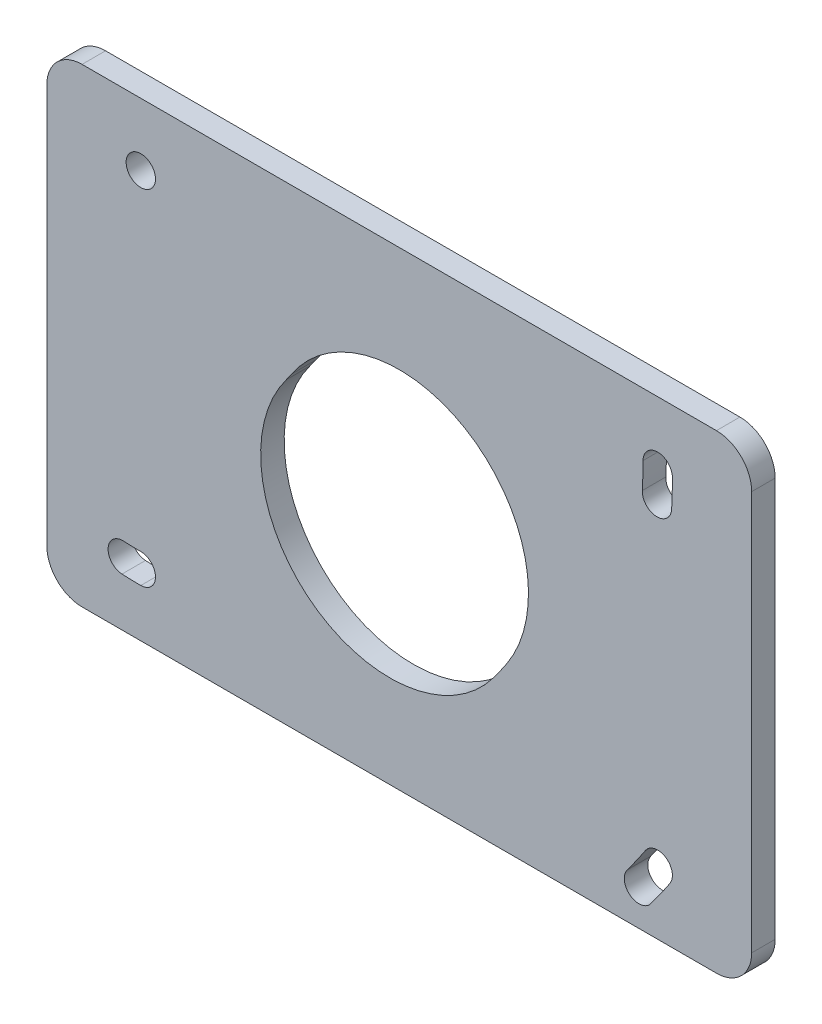
SolidWorks part; units mm, degrees
ref_plane "Płaszczyzna przednia" through (0, 0, 0) normal (0, 0, 1) x (1, 0, 0)
ref_plane "Płaszczyzna górna" through (0, 0, 0) normal (0, 1, 0) x (1, 0, 0)
ref_plane "Płaszczyzna prawa" through (0, 0, 0) normal (1, 0, 0) x (0, 0, -1)
sketch "Szkic1" plane through (0, 0, 0) normal (0, 0, 1) x (1, 0, 0)
  line L0 (-22, 14.6667) -> (-0.7977, -1.1313) construction
  line L1 (-27, -20) -> (27, -20)
  line L2 (-30, -17) -> (-30, 17)
  line L3 (-27, 20) -> (27, 20)
  line L4 (30, -17) -> (30, 17)
  line L5 (-30, -20) -> (30, 20) construction
  line L6 (-30, 20) -> (30, -20) construction
  line L7 (-22, -14.6667) -> (-22, 14.6667) construction
  line L8 (-22, 14.6667) -> (-23.5352, -14.6265) construction
  line L9 (-22, 14.6667) -> (20.4045, -16.9292) construction
  line L10 (22, 14.6667) -> (-22, 14.6667) construction
  line L11 (-22, 14.6667) -> (21.9397, 12.3639) construction
  arc A0 (27, 20) -> (30, 17) centre (27, 17) cw
  arc A1 (27, -20) -> (30, -17) centre (27, -17) ccw
  arc A2 (-27, -20) -> (-30, -17) centre (-27, -17) cw
  arc A3 (-30, 17) -> (-27, 20) centre (-27, 17) cw
  circle A4 centre (-0.7977, -1.1313) radius 11 construction
  circle A5 centre (-22, 14.6667) radius 1.25
  circle A6 centre (21.9397, 12.3639) radius 1.25 construction
  circle A7 centre (-23.5352, -14.6265) radius 1.25 construction
  circle A8 centre (20.4045, -16.9292) radius 1.25 construction
  circle A9 centre (22, -14.6667) radius 1.25 construction
  circle A10 centre (-22, -14.6667) radius 1.25 construction
  circle A11 centre (0, 0) radius 11 construction
  circle A12 centre (22, 14.6667) radius 1.25 construction
  circle A13 centre (-22, 14.6667) radius 26.4407 construction
  circle A14 centre (-22, 14.6667) radius 44 construction
  circle A15 centre (-22, 14.6667) radius 52.8814 construction
  circle A16 centre (-22, 14.6667) radius 29.3333 construction
  arc A17 (20.75, 14.6667) -> (20.6914, 12.4293) centre (-22, 14.6667) cw
  arc A18 (-22, -14.6667) -> (-23.5352, -14.6265) centre (-22, 14.6667) cw construction
  arc A19 (-23.6006, -15.8748) -> (-22, -15.9167) centre (-22, 14.6667) ccw
  arc A20 (-23.4698, -13.3782) -> (-22, -13.4167) centre (-22, 14.6667) ccw
  arc A21 (-23.4698, -13.3782) -> (-23.6006, -15.8748) centre (-23.5352, -14.6265) ccw
  arc A22 (-22, -15.9167) -> (-22, -13.4167) centre (-22, -14.6667) ccw
  arc A23 (22, 14.6667) -> (21.9397, 12.3639) centre (-22, 14.6667) cw construction
  arc A24 (23.188, 12.2985) -> (23.25, 14.6667) centre (-22, 14.6667) ccw
  arc A25 (20.6914, 12.4293) -> (20.75, 14.6667) centre (-22, 14.6667) ccw
  arc A26 (20.6914, 12.4293) -> (23.188, 12.2985) centre (21.9397, 12.3639) ccw
  arc A27 (23.25, 14.6667) -> (20.75, 14.6667) centre (22, 14.6667) ccw
  arc A28 (22, -14.6667) -> (20.4045, -16.9292) centre (-22, 14.6667) cw construction
  arc A29 (21.4069, -17.6761) -> (23.0401, -15.36) centre (-22, 14.6667) ccw
  arc A30 (19.4022, -16.1824) -> (20.9599, -13.9733) centre (-22, 14.6667) ccw
  arc A31 (19.4022, -16.1824) -> (21.4069, -17.6761) centre (20.4045, -16.9292) ccw
  arc A32 (23.0401, -15.36) -> (20.9599, -13.9733) centre (22, -14.6667) ccw
  arc A33 (0, 0) -> (-0.7977, -1.1313) centre (-22, 14.6667) cw construction
  arc A34 (8.0229, -7.7036) -> (9.1526, -6.1017) centre (-22, 14.6667) ccw
  arc A35 (-9.6184, 5.4411) -> (-9.1526, 6.1017) centre (-22, 14.6667) ccw
  arc A36 (-9.6184, 5.4411) -> (8.0229, -7.7036) centre (-0.7977, -1.1313) ccw
  arc A37 (9.1526, -6.1017) -> (-9.1526, 6.1017) centre (0, 0) ccw
  point P0 (0, 0)
  point P40 (-22.7679, -14.6566)
  point P48 (21.9849, 13.5149)
  point P55 (21.2171, -15.8084)
  point P62 (-0.3915, -0.5709)
  dimension "D3" = 3
  dimension "D4" = 2.5
  dimension "D9" = 22
  dimension "D14" = 11
  dimension "D15" = 1.25
  dimension "D16" = 1.25
  dimension "D17" = 1.25
  dimension "D1" = 60
  dimension "D2" = 40
  dimension "D5" = 8
  dimension "D6" = 8
  dimension "D7" = 8
  dimension "D8" = 8
  dimension "D10" = 3
  dimension "D11" = 3
  dimension "D12" = 3
  dimension "D13" = 3
extrude "Dodanie-wyciągnięcie1" add sketch "Szkic1" along normal blind 2 contours A3 L2 A2 L1 A1 L4 A0 L3 A37 A34 A36 A35 A32 A29 A31 A30 A27 A24 A26 A17 A22 A19 A21 A20 A5 region at (-28.6114, -18.6114, 0)
equation "\"D11@Szkic1\"=\"D10@Szkic1\""
equation "\"D12@Szkic1\"=\"D10@Szkic1\""
equation "\"D13@Szkic1\"=\"D10@Szkic1\""
